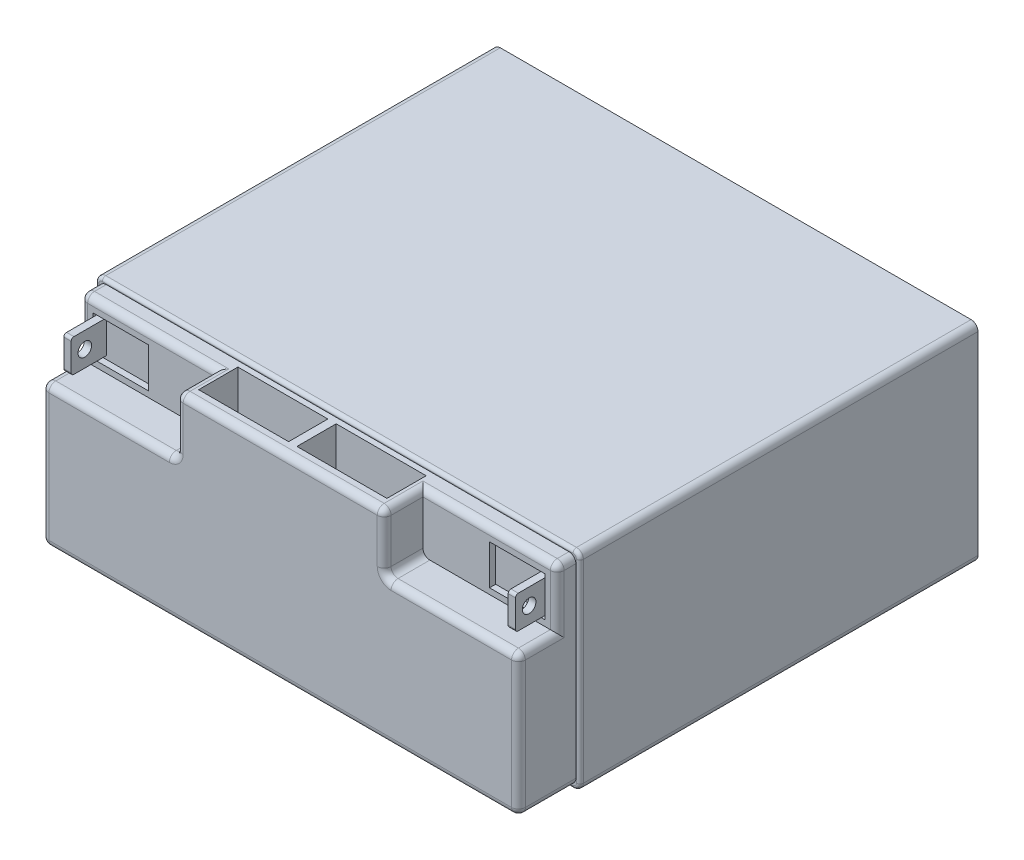
SolidWorks part; units mm, degrees
ref_plane "Front Plane" through (0, 0, 0) normal (0, 0, 1) x (1, 0, 0)
ref_plane "Top Plane" through (0, 0, 0) normal (0, 1, 0) x (1, 0, 0)
ref_plane "Right Plane" through (0, 0, 0) normal (1, 0, 0) x (0, 0, -1)
ref_plane "Plane1" through (0, -62.2132, 0) normal (0, -1, 0) x (1, 0, 0)
sketch "Sketch1" plane through (0, -62.2132, 0) normal (0, -1, 0) x (1, 0, 0)
  line L0 (-33.1131, 0) -> (144.6869, 0)
  line L1 (144.6869, 0) -> (144.6869, 146.05)
  line L2 (144.6869, 146.05) -> (-33.1131, 146.05)
  line L3 (-33.1131, 146.05) -> (-33.1131, 0)
extrude "Boss-Extrude1" add sketch "Sketch1" against normal blind 76.2
sketch "Sketch2" plane through (0, 0, 146.05) normal (0, 0, 1) x (1, 0, 0)
  line L0 (143.2096, -60.7358) -> (-31.6357, -60.7358)
  line L1 (-31.6357, -60.7358) -> (-31.6357, 12.5094)
  line L2 (-31.6357, 12.5094) -> (143.2096, 12.5094)
  line L3 (143.2096, 12.5094) -> (143.2096, -60.7358)
extrude "Boss-Extrude2" add sketch "Sketch2" along normal blind 21.082
sketch "Sketch3" plane through (-31.6357, 0, 0) normal (-1, 0, 0) x (0, 0, 1)
  line L0 (152.908, 12.5094) -> (152.908, -8.8266)
  line L1 (152.908, -8.8266) -> (167.132, -8.8266)
  line L2 (167.132, -8.8266) -> (167.132, 12.5094)
  line L3 (167.132, 12.5094) -> (152.908, 12.5094)
extrude "Cut-Extrude1" cut sketch "Sketch3" against normal blind 49.276
sketch "Sketch4" plane through (0, 0, 152.908) normal (0, 0, 1) x (1, 0, 0)
  line L0 (-24.3791, -5.3674) -> (-27.0726, -5.3674)
  line L1 (-27.0726, -5.3674) -> (-27.0726, 6.6326)
  line L2 (-27.0726, 6.6326) -> (-24.3791, 6.6326)
  line L3 (-24.3791, 6.6326) -> (-24.3791, -5.3674)
extrude "Boss-Extrude3" add sketch "Sketch4" along normal blind 10.746
sketch "Sketch5" plane through (0, 0, 152.908) normal (0, 0, 1) x (1, 0, 0)
  line L0 (-27.0726, 6.6326) -> (-24.3791, 6.6326)
  line L1 (-24.3791, 6.6326) -> (-24.3791, -5.3674)
  line L2 (-24.3791, -5.3674) -> (-27.0726, -5.3674)
  line L3 (-27.0726, -5.3674) -> (-27.0726, -6.6776)
  line L4 (-27.0726, -6.6776) -> (-6.7872, -6.6776)
  line L5 (-6.7872, -6.6776) -> (-6.7872, 7.9428)
  line L6 (-6.7872, 7.9428) -> (-27.0726, 7.9428)
  line L7 (-27.0726, 7.9428) -> (-27.0726, 6.6326)
extrude "Cut-Extrude2" cut sketch "Sketch5" against normal blind 2.254
sketch "Sketch6" plane through (0, 12.5094, 0) normal (0, 1, 0) x (-1, 0, 0)
  line L0 (-143.2096, 152.908) -> (-93.9336, 152.908)
  line L1 (-93.9336, 152.908) -> (-93.9336, 167.132)
  line L2 (-93.9336, 167.132) -> (-143.2096, 167.132)
  line L3 (-143.2096, 167.132) -> (-143.2096, 152.908)
extrude "Cut-Extrude3" cut sketch "Sketch6" against normal blind 21.336
sketch "Sketch7" plane through (0, 0, 152.908) normal (0, 0, 1) x (1, 0, 0)
  line L0 (138.6465, -5.3674) -> (135.9529, -5.3674)
  line L1 (135.9529, -5.3674) -> (135.9529, 6.6326)
  line L2 (135.9529, 6.6326) -> (138.6465, 6.6326)
  line L3 (138.6465, 6.6326) -> (138.6465, -5.3674)
extrude "Boss-Extrude4" add sketch "Sketch7" along normal blind 10.746
sketch "Sketch8" plane through (0, 0, 152.908) normal (0, 0, 1) x (1, 0, 0)
  line L0 (138.6465, -5.3674) -> (135.9529, -5.3674)
  line L1 (135.9529, -5.3674) -> (135.9529, 6.6326)
  line L2 (135.9529, 6.6326) -> (138.6465, 6.6326)
  line L3 (138.6465, 6.6326) -> (138.6465, 7.9428)
  line L4 (138.6465, 7.9428) -> (118.361, 7.9428)
  line L5 (118.361, 7.9428) -> (118.361, -6.6776)
  line L6 (118.361, -6.6776) -> (138.6465, -6.6776)
  line L7 (138.6465, -6.6776) -> (138.6465, -5.3674)
extrude "Cut-Extrude4" cut sketch "Sketch8" against normal blind 2.254
sketch "Sketch9" plane through (0, 12.5094, 0) normal (0, 1, 0) x (-1, 0, 0)
  line L0 (-90.3309, 148.1138) -> (-57.3109, 148.1138)
  line L1 (-57.3109, 148.1138) -> (-57.3109, 162.5135)
  line L2 (-57.3109, 162.5135) -> (-90.3309, 162.5135)
  line L3 (-90.3309, 162.5135) -> (-90.3309, 148.1138)
extrude "Cut-Extrude5" cut sketch "Sketch9" against normal blind 19.05
sketch "Sketch10" plane through (0, 12.5094, 0) normal (0, 1, 0) x (-1, 0, 0)
  line L0 (-54.2629, 148.1138) -> (-21.2429, 148.1138)
  line L1 (-21.2429, 148.1138) -> (-21.2429, 162.5135)
  line L2 (-21.2429, 162.5135) -> (-54.2629, 162.5135)
  line L3 (-54.2629, 162.5135) -> (-54.2629, 148.1138)
extrude "Cut-Extrude6" cut sketch "Sketch10" against normal blind 19.05
sketch "Sketch11" plane through (0, -60.7358, 0) normal (0, -1, 0) x (1, 0, 0)
  line L0 (56.8496, 162.8434) -> (56.8496, 147.6421)
  line L1 (56.8496, 147.6421) -> (120.3496, 147.6421)
  line L2 (120.3496, 147.6421) -> (120.3496, 162.8434)
  line L3 (120.3496, 162.8434) -> (56.8496, 162.8434)
extrude "Cut-Extrude7" cut sketch "Sketch11" against normal blind 19.558
sketch "Sketch12" plane through (0, -60.7358, 0) normal (0, -1, 0) x (1, 0, 0)
  line L0 (-8.7757, 162.8434) -> (-8.7757, 147.6421)
  line L1 (-8.7757, 147.6421) -> (54.7243, 147.6421)
  line L2 (54.7243, 147.6421) -> (54.7243, 162.8434)
  line L3 (54.7243, 162.8434) -> (-8.7757, 162.8434)
extrude "Cut-Extrude8" cut sketch "Sketch12" against normal blind 19.558
hole_wizard "Ø5.0 (5) Diameter Hole1" positions "Sketch14" profile "Sketch13" hole size "Ø5.0" standard "Ansi Metric"
sketch "Sketch14" plane through (135.9529, 0, 0) normal (-1, 0, 0) x (0, 0, 1)
  point P0 (158.654, 0.6326)
sketch "Sketch13" plane through (135.9529, 0.6326, 158.654) normal (0, 1, 0) x (0, 0, 1)
  line L0 (0, 0) -> (0, 8.734)
  line L1 (0, 8.734) -> (2.5, 8.734)
  line L2 (2.5, 8.734) -> (2.5, 0)
  line L5 (2.5, 0) -> (0, 0)
  line L11 (0, -6.35) -> (0, 107.95) construction
  dimension "Thru Hole Dia." = 5
  dimension "Thru Hole Depth" = 8.734
hole_wizard "Ø5.0 (5) Diameter Hole2" positions "Sketch16" profile "Sketch15" hole size "Ø5.0" standard "Ansi Metric"
sketch "Sketch16" plane through (-24.3791, 0, 0) normal (1, 0, 0) x (0, 0, -1)
  point P0 (-158.654, 0.6326)
sketch "Sketch15" plane through (-24.3791, 0.6326, 158.654) normal (0, 1, 0) x (0, 0, -1)
  line L0 (0, 0) -> (0, 8.734)
  line L1 (0, 8.734) -> (2.5, 8.734)
  line L2 (2.5, 8.734) -> (2.5, 0)
  line L5 (2.5, 0) -> (0, 0)
  line L11 (0, -6.35) -> (0, 107.95) construction
  dimension "Thru Hole Dia." = 5
  dimension "Thru Hole Depth" = 8.734
fillet "Fillet1" radius 2.54 26 edges at (143.2096, -60.7358, 156.591) (143.2096, 1.8414, 152.908) (143.2096, 12.5094, 149.479) (-31.6357, -60.7358, 156.591) (55.7869, -60.7358, 167.132) (143.2096, -34.7812, 167.132) (143.2096, -8.8266, 160.02) (118.5716, 12.5094, 152.908) (-31.6357, 12.5094, 149.479) (-31.6357, 1.8414, 152.908) (-31.6357, -8.8266, 160.02) (-31.6357, -34.7812, 167.132) (93.9336, 1.8414, 167.132) (118.5716, -8.8266, 167.132) (93.9336, 12.5094, 160.02) (-6.9977, 12.5094, 152.908) (-6.9977, -8.8266, 167.132) (17.6403, 1.8414, 167.132) (55.7869, 12.5094, 167.132) (17.6403, 12.5094, 160.02) (17.6403, -8.8266, 160.02) (-33.1131, 13.9868, 73.025) (93.9336, -8.8266, 160.02) (144.6869, -62.2132, 73.025) (-33.1131, -62.2132, 73.025) (144.6869, 13.9868, 73.025) tangent propagation no
fillet "Fillet2" radius 1 4 edges at (-25.7258, -5.3674, 163.654) (-25.7258, 6.6326, 163.654) (137.2997, 6.6326, 163.654) (137.2997, -5.3674, 163.654) tangent propagation no
fillet "Fillet3" radius 1.27 8 edges at (-33.1131, -24.1132, 146.05) (-32.3691, 13.2428, 146.05) (-32.3691, -61.4693, 146.05) (55.7869, 13.9868, 146.05) (55.7869, -62.2132, 146.05) (143.943, 13.2428, 146.05) (143.943, -61.4693, 146.05) (144.6869, -24.1132, 146.05) tangent propagation no
ref_plane "Plane2" through (144.6869, 0, 0) normal (1, 0, 0) x (0, 0, -1)
sketch "0_0_Point" plane through (0, 0, 152.908) normal (0, 0, 1) x (1, 0, 0)
  line L0 (-27.0726, -5.3674) -> (-24.3791, 6.6326) construction
  point P0 (-25.7258, 0.6326)
other "0_0" parameters "Diameter"=2, "StubLength"=2
ref_axis "Axis1" through (-25.7258, 0.6326, 162.908) along (0, 0, -1)
sketch "0_1_Point" plane through (0, 0, 152.908) normal (0, 0, 1) x (1, 0, 0)
  line L0 (135.9529, -5.3674) -> (138.6465, 6.6326) construction
  point P0 (137.2997, 0.6326)
other "0_1" parameters "Diameter"=2, "StubLength"=2
ref_axis "Axis2" through (137.2997, 0.6326, 162.908) along (0, 0, -1)
